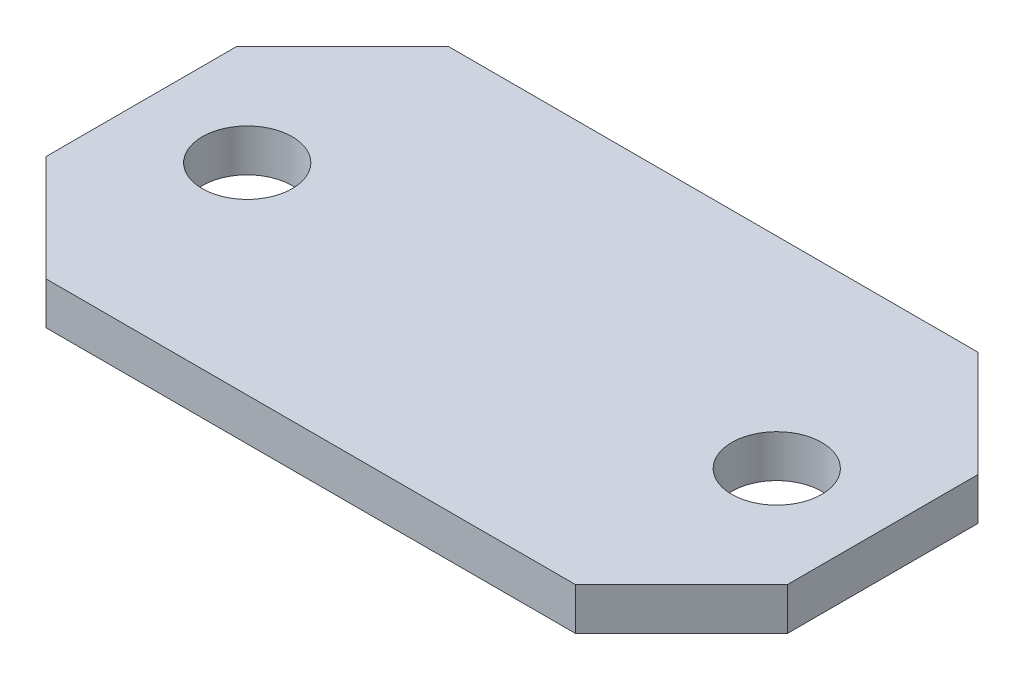
SolidWorks part; units mm, degrees
ref_plane "Płaszczyzna przednia" through (0, 0, 0) normal (0, 0, 1) x (1, 0, 0)
ref_plane "Płaszczyzna górna" through (0, 0, 0) normal (0, 1, 0) x (1, 0, 0)
ref_plane "Płaszczyzna prawa" through (0, 0, 0) normal (1, 0, 0) x (0, 0, -1)
sketch "Szkic1" plane through (0, 0, 0) normal (0, 1, 0) x (1, 0, 0)
  line L0 (-34.674, 0) -> (46.36, 0) construction
  line L1 (35, -9) -> (35, 9)
  line L2 (25, 19) -> (-25, 19)
  line L3 (0, 22.1971) -> (0, -30.5734) construction
  line L4 (25, -19) -> (-25, -19)
  line L5 (-35, -9) -> (-35, 9)
  line L6 (-25, 19) -> (-35, 9)
  line L7 (35, 9) -> (25, 19)
  line L8 (-25, -19) -> (-35, -9)
  line L9 (25, -19) -> (35, -9)
  circle A0 centre (25, 0) radius 4.25
  circle A1 centre (-25, 0) radius 4.25
  point P1 (-35, 19)
  point P4 (35, 19)
  point P6 (0, 0)
  point P10 (35, -19)
  point P11 (35, 0)
  point P12 (-35, -19)
  point P13 (0, -19)
  point P14 (0, 19)
  dimension "D3" = 25
  dimension "D4" = 8.5
  dimension "D9" = 25
  dimension "D10" = 8.5
  dimension "D1" = 70
  dimension "D2" = 38
extrude "Dodanie-wyciągnięcie1" add sketch "Szkic1" along normal blind 4
